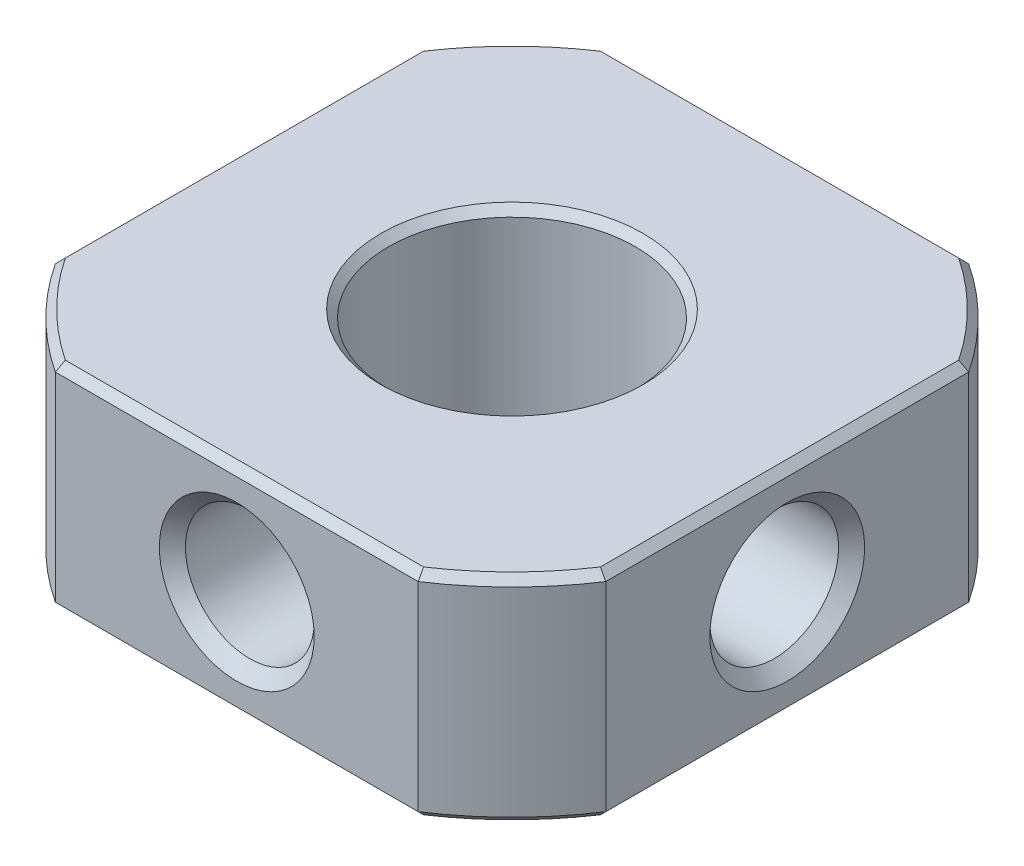
SolidWorks part; units mm, degrees
material "6061-T6 (SS)"
ref_plane "Front" through (0, 0, 0) normal (0, 0, 1) x (1, 0, 0)
ref_plane "Top" through (0, 0, 0) normal (0, 1, 0) x (1, 0, 0)
ref_plane "Right" through (0, 0, 0) normal (1, 0, 0) x (0, 0, -1)
sketch "Sketch1" plane through (0, 0, 0) normal (0, 1, 0) x (1, 0, 0)
  line L4 (-5.9171, 8.975) -> (5.9171, 8.975)
  line L5 (8.975, 5.9171) -> (8.975, -5.9171)
  line L6 (5.9171, -8.975) -> (-5.9171, -8.975)
  line L7 (-8.975, -5.9171) -> (-8.975, 5.9171)
  line L8 (0, 8.975) -> (0, 0) construction
  line L9 (0, 0) -> (8.975, 0) construction
  arc A4 (8.975, 5.9171) -> (5.9171, 8.975) centre (0, 0) ccw
  arc A5 (5.9171, -8.975) -> (8.975, -5.9171) centre (0, 0) ccw
  arc A6 (-8.975, -5.9171) -> (-5.9171, -8.975) centre (0, 0) ccw
  arc A7 (-5.9171, 8.975) -> (-8.975, 5.9171) centre (0, 0) ccw
  circle A9 centre (0, 0) radius 4.025
  dimension "D1" = 8.05
  dimension "D2" = 10.75
  dimension "D3" = 17.95
  dimension "D4" = 17.95
extrude "Boss-Extrude1" add sketch "Sketch1" along normal blind 7 separate body
chamfer "Chamfer1" distance 0.25 angle 45 18 edges at (0, 0, 4.025) (-8.975, 0, 0) (-7.6014, 0, 7.6014) (0, 0, 8.975) (7.6014, 0, 7.6014) (8.975, 0, 0) (7.6014, 0, -7.6014) (0, 0, -8.975) (-7.6014, 0, -7.6014) (0, 7, 4.025) (0, 7, -8.975) (7.6014, 7, -7.6014) (8.975, 7, 0) (7.6014, 7, 7.6014) (0, 7, 8.975) (-7.6014, 7, 7.6014) (-8.975, 7, 0) (-7.6014, 7, -7.6014)
hole_wizard "M5 Tapped Hole1" positions "Sketch3" profile "Sketch2" tap size "M5" standard "ISO" end condition up to next
sketch "Sketch3" plane through (8.975, 0, 0) normal (1, 0, 0) x (0, 0, -1)
  line L0 (-5.9171, 6.75) -> (-5.9171, 0.25) construction
  point P0 (0, 3.5)
  point P4 (-5.9171, 3.5)
sketch "Sketch2" plane through (8.975, 3.5, 0) normal (0, 1, 0) x (0, 0, -1)
  line L0 (0, 0) -> (0, 4.95)
  line L1 (0, 4.95) -> (2.1, 4.95)
  line L2 (2.1, 4.95) -> (2.1, 0.425)
  line L3 (2.1, 0.425) -> (2.525, 0)
  line L5 (2.525, 0) -> (0, 0)
  line L6 (-2.1, 0.425) -> (-2.525, 0) construction
  line L11 (0, -6.35) -> (0, 107.95) construction
  dimension "Thru Tap Drill Dia." = 4.2
  dimension "Thru Tap Drill Depth" = 4.95
  dimension "Near C'Sink Dia." = 5.05
  dimension "Near C'Sink Angle" = 90
cosmetic thread "Hole Thread1" parameters "D2"=5
hole_wizard "M5 Tapped Hole2" positions "Sketch5" profile "Sketch4" tap size "M5" standard "ISO" end condition up to next
sketch "Sketch5" plane through (0, 0, 8.975) normal (0, 0, 1) x (1, 0, 0)
  line L0 (5.9171, 6.75) -> (5.9171, 0.25) construction
  point P0 (0, 3.5)
  point P6 (5.9171, 3.5)
sketch "Sketch4" plane through (0, 3.5, 8.975) normal (1, 0, 0) x (0, -1, 0)
  line L0 (0, 0) -> (0, 4.95)
  line L1 (0, 4.95) -> (2.1, 4.95)
  line L2 (2.1, 4.95) -> (2.1, 0.425)
  line L3 (2.1, 0.425) -> (2.525, 0)
  line L5 (2.525, 0) -> (0, 0)
  line L6 (-2.1, 0.425) -> (-2.525, 0) construction
  line L11 (0, -6.35) -> (0, 107.95) construction
  dimension "Thru Tap Drill Dia." = 4.2
  dimension "Thru Tap Drill Depth" = 4.95
  dimension "Near C'Sink Dia." = 5.05
  dimension "Near C'Sink Angle" = 90
cosmetic thread "Hole Thread2" parameters "D2"=5
